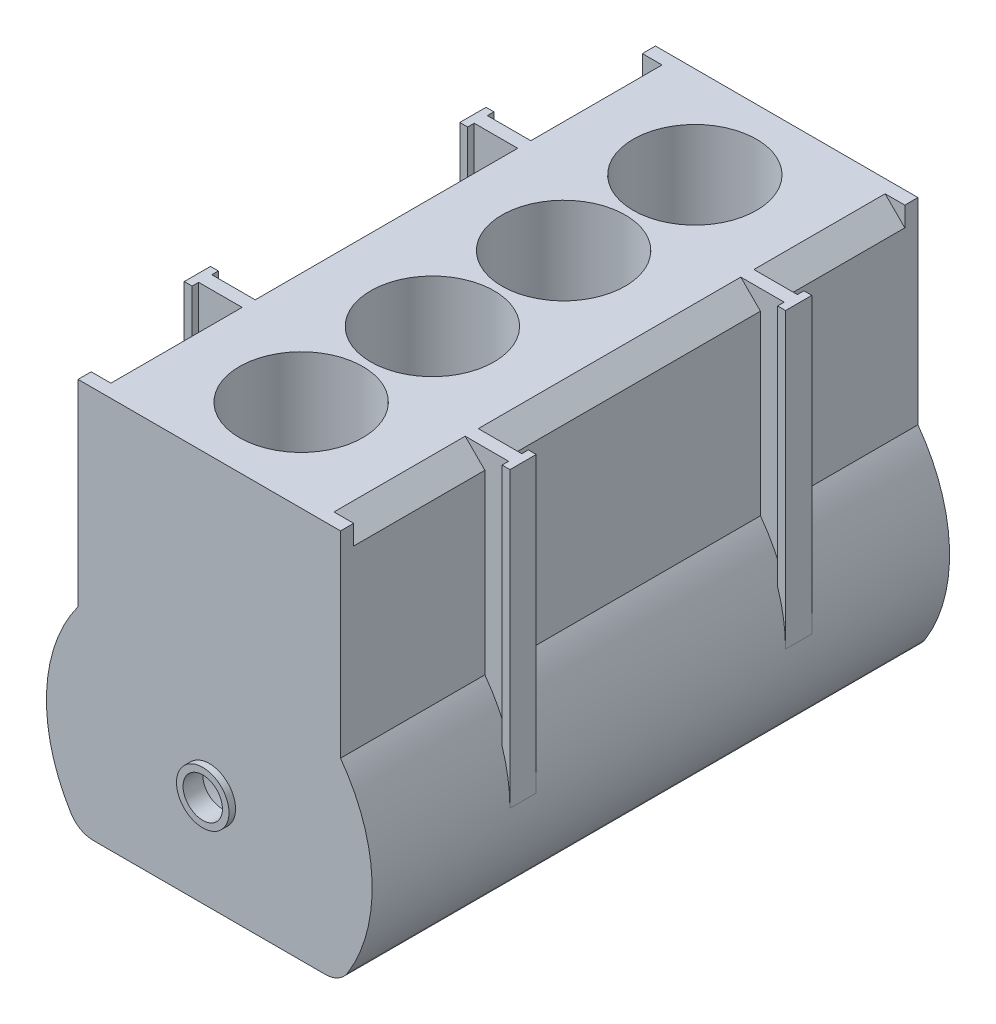
SolidWorks part; units mm, degrees
ref_plane "Front Plane" through (0, 0, 0) normal (0, 0, 1) x (1, 0, 0)
ref_plane "Top Plane" through (0, 0, 0) normal (0, 1, 0) x (1, 0, 0)
ref_plane "Right Plane" through (0, 0, 0) normal (1, 0, 0) x (0, 0, -1)
sketch "Sketch1" plane through (0, 0, 0) normal (0, 0, 1) x (1, 0, 0)
  line L0 (-100, 73.5) -> (-100, 223.5)
  line L1 (-100, 223.5) -> (100, 223.5)
  line L2 (100, 223.5) -> (100, 73.5)
  line L4 (-88.3913, -75) -> (88.3913, -75)
  circle A0 centre (0, 0) radius 15
  circle A1 centre (0, 0) radius 20
  arc A3 (-100, 73.5) -> (-105.3723, -65.5662) centre (0, 0) ccw
  arc A4 (105.3723, -65.5662) -> (100, 73.5) centre (0, 0) ccw
  arc A5 (88.3913, -75) -> (105.3723, -65.5662) centre (88.3913, -55) ccw
  arc A6 (-88.3913, -75) -> (-105.3723, -65.5662) centre (-88.3913, -55) cw
  point P12 (98.88, -75)
  dimension "D1" = 30
  dimension "D2" = 40
  dimension "D5" = 20
  dimension "D3" = 75
  dimension "D4" = 200
  dimension "D6" = 73.5
extrude "Boss-Extrude1" add sketch "Sketch1" along normal blind 10 contours A1 A0 | A1 L2 L1 L0 region at (0, 70.1453, 0) region at (-19.4343, 0, 0)
sketch "Sketch2" plane through (0, 0, 10) normal (0, 0, 1) x (1, 0, 0)
  line L1 (-100, 223.5) -> (100, 223.5)
  line L2 (-100, 223.5) -> (-100, 73.5)
  line L3 (-100, 73.5) -> (100, 73.5)
  line L4 (100, 223.5) -> (100, 73.5)
  line L6 (-100, 223.5) -> (100, 223.5) construction
  point P7 (0, 223.5)
  dimension "D1" = 150
  dimension "D2" = 200
  dimension "D3" = 100
extrude "Boss-Extrude2" add sketch "Sketch2" along normal blind 420 separate body
sketch "Sketch3" plane through (0, 223.5, 0) normal (0, 1, 0) x (1, 0, 0)
  line L0 (-100, -10) -> (100, -10) construction
  line L1 (100, -10) -> (-100, -10) construction
  line L6 (100, -430) -> (100, -10) construction
  circle A0 centre (0, -370) radius 47
  circle A1 centre (0, -270) radius 47
  circle A2 centre (0, -170) radius 47
  circle A3 centre (0, -70) radius 47
  point P10 (0, -117)
  point P11 (0, -123)
  point P12 (47, -70)
  point P13 (0, -23)
  point P14 (0, -417)
  point P18 (-47, -70)
  point P19 (0, -10)
  dimension "D2" = 94
  dimension "D4" = 94
  dimension "D5" = 94
  dimension "D7" = 94
  dimension "D1" = 60
  dimension "D3" = 100
  dimension "D6" = 100
  dimension "D8" = 100
  dimension "D9" = 53
extrude "Cut-Extrude1" cut sketch "Sketch3" against normal blind 150
ref_plane "Plane1" through (0, 223.5, 0) normal (0, 1, 0) x (1, 0, 0)
chamfer "Chamfer2" distance 15 angle 45 2 edges at (-100, 223.5, 220) (100, 223.5, 220)
sketch "Sketch4" plane through (0, 0, 0) normal (0, 0, 1) x (1, 0, 0)
  line L0 (88.3913, -75) -> (-88.3913, -75)
  line L3 (-100, 73.5) -> (100, 73.5) construction
  line L5 (-65, 0) -> (-65, 63.5)
  line L6 (65, 0) -> (65, 63.5)
  line L8 (-100, 73.5) -> (-55, 73.5)
  line L9 (55, 73.5) -> (100, 73.5)
  arc A0 (105.3723, -65.5662) -> (100, 73.5) centre (0, 0) ccw
  arc A2 (88.3913, -75) -> (105.3723, -65.5662) centre (88.3913, -55) ccw
  arc A4 (-88.3913, -75) -> (-105.3723, -65.5662) centre (-88.3913, -55) cw
  arc A6 (-100, 73.5) -> (-105.3723, -65.5662) centre (0, 0) ccw
  arc A8 (-65, 0) -> (65, 0) centre (0, 0) ccw
  arc A9 (65, 63.5) -> (55, 73.5) centre (55, 63.5) ccw
  arc A10 (-65, 63.5) -> (-55, 73.5) centre (-55, 63.5) cw
  point P5 (114.1058, 0)
  point P6 (124.1058, 0)
  point P11 (98.88, -75)
  point P17 (-65, 73.5)
  dimension "D3" = 20
  dimension "D4" = 10
  dimension "D5" = 10
  dimension "D1" = 10
  dimension "D2" = 75
extrude "Boss-Extrude3" add sketch "Sketch4" along normal blind 420 from offset 10
sketch "Sketch5" plane through (0, 0, 0) normal (0, 0, 1) x (1, 0, 0)
  line L0 (-124.1058, 0) -> (-85, 0)
  line L1 (124.1058, 0) -> (124.1058, 223.5)
  line L2 (149.3774, 223.5) -> (-149.3774, 223.5) construction
  line L3 (-124.1058, 0) -> (-124.1058, 223.5)
  line L4 (-124.1058, 223.5) -> (-85, 223.5)
  line L5 (124.1058, 223.5) -> (85, 223.5)
  line L6 (85, 223.5) -> (85, 0)
  line L7 (-85, 223.5) -> (-85, 0)
  line L8 (-118.1058, 223.5) -> (-118.1058, 0)
  line L9 (118.1058, 223.5) -> (118.1058, 0)
  line L10 (85, 0) -> (124.1058, 0)
  arc A0 (105.3723, -65.5662) -> (100, 73.5) centre (0, 0) ccw construction
  arc A1 (-100, 73.5) -> (-105.3723, -65.5662) centre (0, 0) ccw construction
  dimension "D1" = 6
  dimension "D2" = 6
extrude "Boss-Extrude4" add sketch "Sketch5" along normal blind 5 and the other way blind 5 from offset 115 contours L6 L10 L1 L5 | L3 L4 L7 L0
extrude "Boss-Extrude5" add sketch "Sketch5<3>" along normal blind 5 and the other way blind 5 from offset 325 contours L1 L5 L6 L10 | L0 L7 L4 L3
sketch "Sketch5<3>" plane through (0, 0, 0) normal (0, 0, 1) x (1, 0, 0) same geometry as "Sketch5"
extrude "Boss-Extrude6" add sketch "Sketch5<4>" along normal blind 10 and the other way blind 10 from offset 115 contours L9 L10 L1 L5 | L8 L4 L3 L0 region at (-121.1058, 111.75, 0) region at (121.1058, 111.75, 0)
sketch "Sketch5<4>" plane through (0, 0, 0) normal (0, 0, 1) x (1, 0, 0) same geometry as "Sketch5"
extrude "Boss-Extrude7" add sketch "Sketch5<5>" along normal blind 10 and the other way blind 10 from offset 325 contours L8 L4 L3 L0 | L9 L10 L1 L5 region at (-121.1058, 111.75, 0) region at (121.1058, 111.75, 0)
sketch "Sketch5<5>" plane through (0, 0, 0) normal (0, 0, 1) x (1, 0, 0) same geometry as "Sketch5"
sketch "Sketch10" plane through (0, 0, 430) normal (0, 0, 1) x (1, 0, 0)
  line L0 (-100, 223.5) -> (100, 223.5)
  line L2 (100, 223.5) -> (100, 73.5)
  line L4 (-100, 223.5) -> (-100, 73.5)
  line L7 (85, 223.5) -> (-85, 223.5) construction
  line L8 (-88.3913, -75) -> (88.3913, -75)
  line L9 (-88.3913, -75) -> (88.3913, -75) construction
  arc A0 (-100, 73.5) -> (-105.3723, -65.5662) centre (0, 0) ccw
  arc A1 (105.3723, -65.5662) -> (100, 73.5) centre (0, 0) ccw
  arc A2 (88.3913, -75) -> (105.3723, -65.5662) centre (88.3913, -55) ccw
  arc A3 (-88.3913, -75) -> (-105.3723, -65.5662) centre (-88.3913, -55) cw
  circle A4 centre (0, 0) radius 15
  circle A5 centre (0, 0) radius 20
  point P18 (98.88, -75)
  point P23 (-98.88, -75)
  dimension "D1" = 20
  dimension "D2" = 40
extrude "Boss-Extrude8" add sketch "Sketch10" along normal blind 10 contours A4 | A1 L2 L0 L4 A0 A3 L8 A2 region at (0, 0, 430)
extrude "Boss-Extrude9" add sketch "Sketch10<3>" along normal blind 15 contours A5 A4 region at (-19.4343, 0, 430)
sketch "Sketch10<3>" plane through (0, 0, 430) normal (0, 0, 1) x (1, 0, 0) same geometry as "Sketch10"
